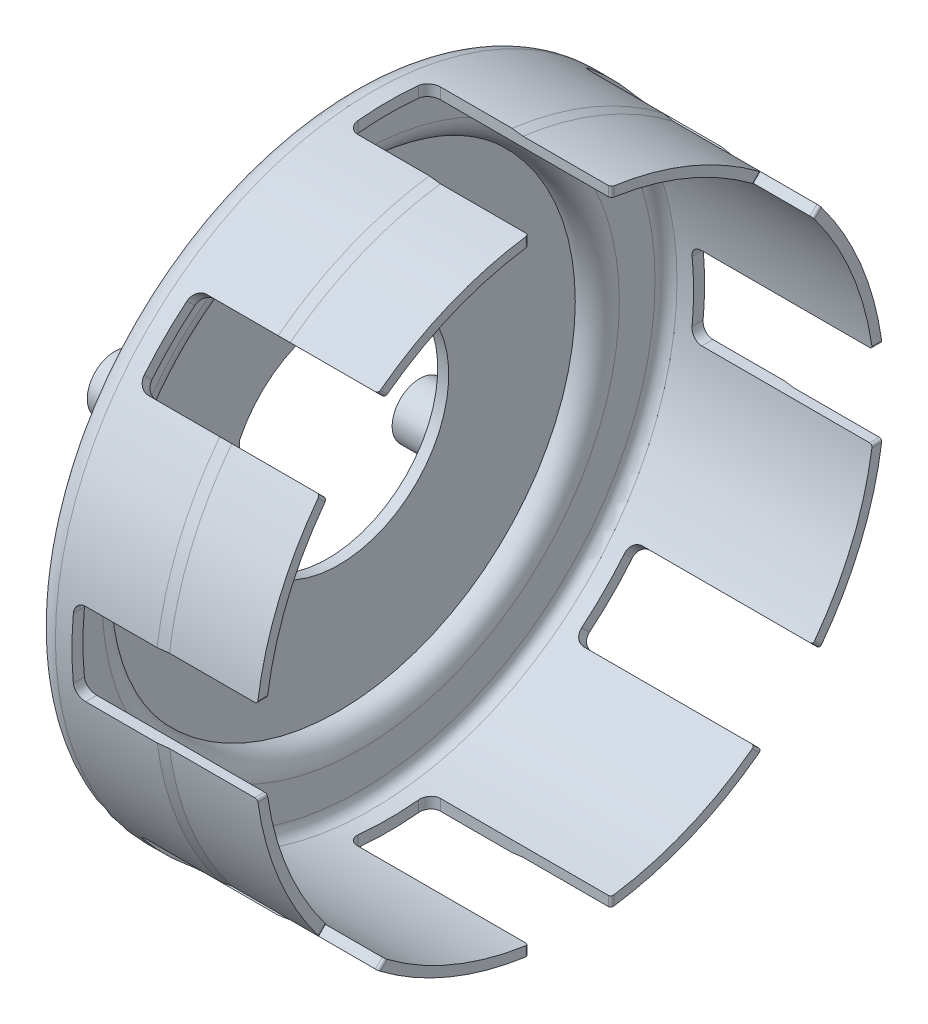
SolidWorks part; units mm, degrees
material "7075-T6 (SN)"
ref_plane "Front Plane" through (0, 0, 0) normal (1, 0, 0) x (0, 1, 0)
ref_plane "Top Plane" through (0, 0, 0) normal (0, 0, 1) x (0, 1, 0)
ref_plane "Right Plane" through (0, 0, 0) normal (0, 1, 0) x (-1, 0, 0)
sketch "Sketch1" plane through (0, 0, 0) normal (0, 1, 0) x (-1, 0, 0)
  line L0 (-113.8457, 0) -> (159.6617, 0) construction
  line L1 (0, 91.979) -> (0, -92.6732) construction
  line L2 (0, 57.5) -> (40, 57.5)
  line L3 (40, 57.5) -> (40, 45)
  line L4 (40, 45) -> (44, 45)
  line L5 (44, 45) -> (44, 0)
  line L6 (44, 0) -> (0, 0)
  line L7 (0, 57.5) -> (0, 0)
  dimension "D1" = 45
  dimension "D2" = 57.5
  dimension "D3" = 4
  dimension "D4" = 40
revolve "Revolve2" add sketch "Sketch1" angle 360 about L0
fillet "Fillet1" radius 4 1 edges at (-40, 0, -57.5)
fillet "Fillet2" radius 2 2 edges at (-44, 0, -45) (-40, 0, -45)
shell "Shell1" thickness 2 removed face at (0, 0, -57.5)
sketch "Sketch2" plane through (-44, 0, 0) normal (-1, 0, 0) x (0, -1, 0)
  line L0 (-8.7178, 18) -> (8.7178, 18)
  arc A0 (-8.7178, 18) -> (8.7178, 18) centre (0, 0) ccw
  circle A1 centre (32, 0) radius 5
  circle A2 centre (32, 0) radius 2
  dimension "D1" = 40
  dimension "D4" = 10
  dimension "D5" = 4
  dimension "D2" = 18
  dimension "D3" = 32
extrude "Cut-Extrude1" cut sketch "Sketch2" against normal through all contours L0 A0 region at (-44, 0, -0.3582)
extrude "Boss-Extrude1" add sketch "Sketch2<3>" along normal blind 11 from surface contours A1 A2 region at (-44, -27.1414, 0) starting at face at (-44, 0, -43)
sketch "Sketch2<3>" plane through (-44, 0, 0) normal (-1, 0, 0) x (0, -1, 0) same geometry as "Sketch2"
fillet "Fillet3" radius 0.5 1 edges at (-44, -32, -5)
pattern_circular "CirPattern1" count 6 over 360 about axis through (-44, 0, 0) along (-1, 0, 0) of "Boss-Extrude1", "Fillet3"
sketch "Sketch3" plane through (0, 0, 0) normal (0, 1, 0) x (-1, 0, 0)
  line L0 (0, 57.5) -> (0, -57.5) construction
  line L1 (0, 7.5) -> (31, 7.5)
  line L2 (0, 7.5) -> (0, -7.5)
  line L3 (0, -7.5) -> (31, -7.5)
  line L4 (33, 5.5) -> (33, -5.5)
  arc A0 (31, -7.5) -> (33, -5.5) centre (31, -5.5) ccw
  arc A1 (31, 7.5) -> (33, 5.5) centre (31, 5.5) cw
  point P7 (33, -7.5)
  dimension "D4" = 2
  dimension "D1" = 15
  dimension "D2" = 7.5
  dimension "D3" = 33
extrude "Cut-Extrude2" cut sketch "Sketch3" against normal through all
fillet "Fillet4" radius 0.5 2 edges at (0, -55.9998, 7.5) (0, -55.9998, -7.5)
pattern_circular "CirPattern2" count 8 over 360 about axis through (0, 0, 0) along (1, 0, 0) of "Cut-Extrude2", "Fillet4"
sketch "Sketch6" plane through (0, 0, 0) normal (0, 0, 1) x (0, 1, 0)
  line L5 (0, 17.2324) -> (0, -15.2442) construction
  line L6 (-69.9065, 0) -> (6.469, 0) construction
  line L10 (-57.5, 36) -> (-57.5, 33) construction
  line L12 (-57.5, 36) -> (-57.5, -1.2702) construction
  line L14 (-57.5, 18) -> (-57.25, 16)
  line L15 (-57.5, 0) -> (-57.25, 0)
  line L16 (-57.5, 0) -> (-57.5, 18)
  line L17 (-57.5, 18) -> (-57.25, 18)
  line L18 (-57.25, 0) -> (-57.25, 16)
  point P0 (-57.5, 0)
  dimension "D1" = 0.25
  dimension "D2" = 18
  dimension "D3" = 2
revolve "Cut-Revolve5" cut sketch "Sketch6" angle 360 about L5
ref_axis "Axis1" through (-110.3104, 0, 0) along (1, 0, 0)
